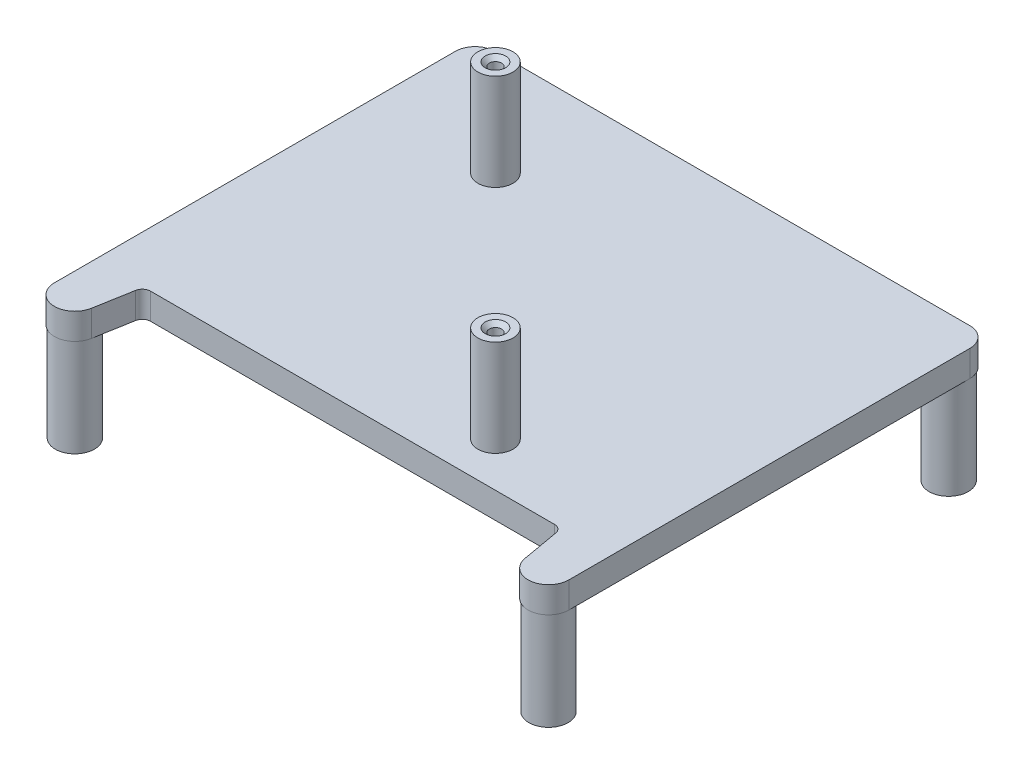
SolidWorks part; units mm, degrees
ref_plane "Front Plane" through (0, 0, 0) normal (0, 0, 1) x (1, 0, 0)
ref_plane "Top Plane" through (0, 0, 0) normal (0, 1, 0) x (1, 0, 0)
ref_plane "Right Plane" through (0, 0, 0) normal (1, 0, 0) x (0, 0, -1)
sketch "Sketch1" plane through (0, 0, 0) normal (0, 1, 0) x (1, 0, 0)
  line L0 (-31.5, 0) -> (31.5, 0) construction
  line L1 (-31.5, 27) -> (31.5, 27)
  line L2 (-31.5, 27) -> (-31.5, -27)
  line L3 (-31.5, -27) -> (31.5, -27)
  line L4 (31.5, 27) -> (31.5, -27)
  line L5 (0, 27) -> (0, -27) construction
  line L6 (-25, -23.25) -> (25, -23.25) construction
  line L7 (-25, -19.5) -> (25, -19.5)
  line L8 (-25, -19.5) -> (-25, -27)
  line L9 (-25, -27) -> (25, -27)
  line L10 (25, -19.5) -> (25, -27)
  line L11 (0, -19.5) -> (0, -27) construction
  point P8 (0, 0)
  dimension "D1" = 63
  dimension "D2" = 54
  dimension "D3" = 7.5
  dimension "D4" = 50
extrude "Boss-Extrude1" add sketch "Sketch1" along normal blind 3.2 contours L7 L10 L3 L4 L1 L2 L8 region at (0, 0, -2.8803)
sketch "Sketch2" plane through (0, 0, 0) normal (0, -1, 0) x (1, 0, 0)
  line L0 (0, 19.5) -> (0, -27) construction
  line L1 (-25, 19.5) -> (25, 19.5) construction
  line L2 (-31.5, -27) -> (31.5, -27) construction
  line L3 (-31.5, 0) -> (31.5, 0) construction
  line L4 (-31.5, -27) -> (-31.5, 27) construction
  line L5 (31.5, -27) -> (31.5, 27) construction
  circle A0 centre (-29, -24.5) radius 0.75
  circle A1 centre (29, -24.5) radius 0.75
  circle A2 centre (-29, 24.5) radius 0.75
  circle A3 centre (29, 24.5) radius 0.75
  circle A4 centre (-29, -24.5) radius 2.4
  circle A5 centre (29, -24.5) radius 2.4
  circle A6 centre (29, 24.5) radius 2.4
  circle A7 centre (-29, 24.5) radius 2.4
  dimension "D1" = 1.5
  dimension "D2" = 58
  dimension "D4" = 4.8
  dimension "D3" = 49
extrude "Boss-Extrude2" add sketch "Sketch2" along normal blind 12
sketch "Sketch3" plane through (0, 3.2, 0) normal (0, 1, 0) x (1, 0, 0)
  line L0 (-31.5, 0) -> (31.5, 0) construction
  line L1 (-31.5, 27) -> (-31.5, -27) construction
  line L2 (31.5, 27) -> (31.5, -27) construction
  line L3 (0, 27) -> (0, -19.5) construction
  line L4 (-31.5, 27) -> (31.5, 27) construction
  line L5 (-25, -19.5) -> (25, -19.5) construction
  circle A0 centre (-16.125, 14.125) radius 0.75
  circle A1 centre (-16.125, 14.125) radius 2.15
  circle A4 centre (12.075, -14.075) radius 0.75
  circle A5 centre (12.075, -14.075) radius 2.15
  dimension "D1" = 4.3
  dimension "D2" = 1.5
  dimension "D3" = 28.2
  dimension "D4" = 28.2
  dimension "D5" = 12.875
  dimension "D6" = 15.375
extrude "Boss-Extrude3" add sketch "Sketch3" along normal blind 11.8
chamfer "Chamfer1" distance 0.5 angle 45 6 edges at (-29, -12, 25.25) (29, -12, 23.75) (29, -12, -23.75) (-29, -12, -25.25) (-16.125, 15, -13.375) (12.075, 15, 14.825)
chamfer "Chamfer2" distance 1.9 angle 80 2 edges at (25, 1.6, 27) (-25, 1.6, 27) first distance on face at (28.25, 1.6, 27) first distance on face at (-28.25, 1.6, 27)
fillet "Fillet1" radius 2.4 2 edges at (-31.5, 1.6, -27) (31.5, 1.6, -27)
fillet "Fillet2" 2 edges at (31.5, 1.6, 27) (26.9, 1.6, 27) type full round first side face at (31.5, 1.6, 1.2) second side face at (26.2388, 1.6, 23.25) middle face at (29.2, 1.6, 27)
fillet "Fillet3" 2 edges at (-31.5, 1.6, 27) (-26.9, 1.6, 27) type full round first side face at (-31.5, 1.6, 1.2) second side face at (-26.2388, 1.6, 23.25) middle face at (-29.2, 1.6, 27)
fillet "Fillet4" radius 1 2 edges at (25.5775, 1.6, 19.5) (-25.5775, 1.6, 19.5)
